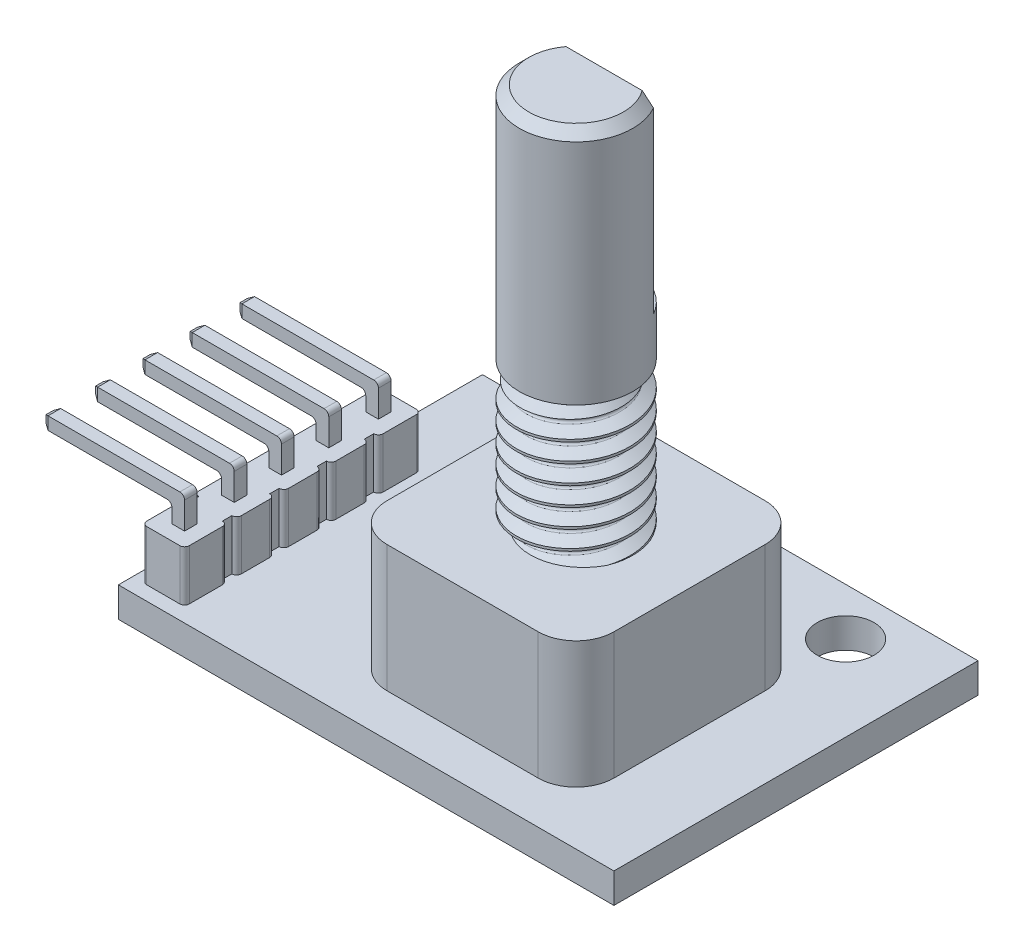
SolidWorks part; units mm, degrees
note: The reader was unsure of these and kept them because the rebuilt part matched: shared geometry of "Esboço2<2>", "Esboço6<3>", "Esboço6<4>".
ref_plane "Plano frontal" through (0, 0, 0) normal (0, 0, 1) x (1, 0, 0)
ref_plane "Plano superior" through (0, 0, 0) normal (0, 1, 0) x (1, 0, 0)
ref_plane "Plano direito" through (0, 0, 0) normal (1, 0, 0) x (0, 0, -1)
sketch "Esboço2" plane through (0, 0, 0) normal (0, 1, 0) x (1, 0, 0)
  line L5 (-6, 6) -> (6, 6)
  line L6 (-6, 6) -> (-6, -6)
  line L7 (-6, -6) -> (6, -6)
  line L8 (6, 6) -> (6, -6)
  line L9 (-6, 6) -> (6, -6) construction
  line L10 (-6, -6) -> (6, 6) construction
  line L11 (-15.95, 11) -> (10.25, 11)
  line L12 (-15.95, 11) -> (-15.95, -8.25)
  line L13 (-15.95, -8.25) -> (10.25, -8.25)
  line L14 (10.25, 11) -> (10.25, -8.25)
  line L15 (-15.95, 11) -> (10.25, -8.25) construction
  line L16 (-15.95, -8.25) -> (10.25, 11) construction
  circle A0 centre (-11.15, 8.5) radius 1.5
  circle A1 centre (5.75, 8.5) radius 1.5
  point P0 (0, 0)
  dimension "D7" = 3
  dimension "D8" = 2.5
  dimension "D9" = 4.5
  dimension "D10" = 16.9
  dimension "D1" = 26.2
  dimension "D2" = 19.25
  dimension "D3" = 12
  dimension "D4" = 12
  dimension "D5" = 5
  dimension "D6" = 4.25
extrude "Ressalto-extrusão1" add sketch "Esboço2" along normal blind 1.58
extrude "Ressalto-extrusão2" add sketch "Esboço2<2>" along normal offset from surface (8.28 mm away) 6.7 contours L8 L5 L6 L7 up to face at (-11.15, 1.58, -7) offset beyond the face yes
sketch "Esboço2<2>" plane through (0, 0, 0) normal (0, 1, 0) x (1, 0, 0) same geometry as "Esboço2"
sketch "Esboço3" plane through (0, 1.58, 0) normal (0, 1, 0) x (1, 0, 0)
  line L0 (-15.45, 2.5) -> (-13.2, 2.5) construction
  line L1 (-15.45, 5) -> (-13.2, 5)
  line L2 (-15.45, 5) -> (-15.45, 2.75)
  line L3 (-15.45, -7.5) -> (-13.2, -7.5)
  line L4 (-13.2, 5) -> (-13.2, 2.75)
  line L5 (-15.45, 0) -> (-13.2, 0) construction
  line L6 (10.25, 11) -> (-15.95, 11) construction
  line L7 (-15.45, -2.5) -> (-13.2, -2.5) construction
  line L9 (-15.45, -5) -> (-13.2, -5) construction
  line L10 (-15.45, 2.25) -> (-15.2, 2.25)
  line L11 (-15.45, -0.25) -> (-15.2, -0.25)
  line L12 (-15.45, -2.75) -> (-15.2, -2.75)
  line L13 (-15.45, -5.25) -> (-15.2, -5.25)
  line L14 (-15.45, 2.75) -> (-15.2, 2.75)
  line L15 (-15.45, 0.25) -> (-15.2, 0.25)
  line L16 (-15.45, -2.25) -> (-15.2, -2.25)
  line L17 (-15.45, -4.75) -> (-15.2, -4.75)
  line L18 (-15.2, 2.75) -> (-15.2, 2.25)
  line L19 (-13.45, 2.75) -> (-13.45, 2.25)
  line L20 (-15.45, 2.25) -> (-15.45, 0.25)
  line L21 (-13.2, 2.25) -> (-13.2, 0.25)
  line L22 (-13.45, 2.25) -> (-13.2, 2.25)
  line L23 (-13.45, 2.75) -> (-13.2, 2.75)
  line L24 (-15.45, 2.25) -> (-13.2, 2.25) construction
  line L25 (-15.2, 0.25) -> (-15.2, -0.25)
  line L26 (-15.45, 2.75) -> (-13.2, 2.75) construction
  line L27 (-13.45, 0.25) -> (-13.45, -0.25)
  line L28 (-13.45, 0.25) -> (-13.2, 0.25)
  line L29 (-13.2, -0.25) -> (-13.2, -2.25)
  line L30 (-15.45, 0.25) -> (-13.2, 0.25) construction
  line L31 (-13.45, -0.25) -> (-13.2, -0.25)
  line L32 (-13.45, -2.25) -> (-13.45, -2.75)
  line L33 (-15.45, -0.25) -> (-13.2, -0.25) construction
  line L34 (-13.2, -2.75) -> (-13.2, -4.75)
  line L35 (-13.45, -2.25) -> (-13.2, -2.25)
  line L36 (-13.45, -2.75) -> (-13.2, -2.75)
  line L37 (-15.45, -2.25) -> (-13.2, -2.25) construction
  line L38 (-13.45, -4.75) -> (-13.45, -5.25)
  line L39 (-15.45, -2.75) -> (-13.2, -2.75) construction
  line L40 (-13.45, -4.75) -> (-13.2, -4.75)
  line L41 (-13.2, -5.25) -> (-13.2, -7.5)
  line L42 (-15.45, -4.75) -> (-13.2, -4.75) construction
  line L43 (-13.45, -5.25) -> (-13.2, -5.25)
  line L44 (-15.45, -5.25) -> (-15.45, -7.5)
  line L45 (-15.45, -5.25) -> (-13.2, -5.25) construction
  line L46 (-15.2, -4.75) -> (-15.2, -5.25)
  line L47 (-15.45, -0.25) -> (-15.45, -2.25)
  line L48 (-15.2, -2.25) -> (-15.2, -2.75)
  line L49 (-15.45, -2.75) -> (-15.45, -4.75)
  line L50 (-15.95, 11) -> (-15.95, -8.25) construction
  dimension "D1" = 12.5
  dimension "D2" = 2.25
  dimension "D3" = 2.25
  dimension "D4" = 2.5
  dimension "D5" = 2.5
  dimension "D6" = 2.5
  dimension "D7" = 6
  dimension "D8" = 0.5
  dimension "D9" = 2.25
  dimension "D12" = 0.25
  dimension "D13" = 0.25
  dimension "D10" = 0.25
  dimension "D11" = 0.25
extrude "Ressalto-extrusão3" add sketch "Esboço3" along normal offset from surface (2.67 mm away) 4.25 up to face at (-2.85, 0, -1.375)
fillet "Filete1" radius 0.25 20 edges at (-13.2, 2.915, -5) (-13.2, 2.915, -2.75) (-13.2, 2.915, -2.25) (-13.2, 2.915, -0.25) (-13.2, 2.915, 0.25) (-13.2, 2.915, 2.25) (-13.2, 2.915, 2.75) (-13.2, 2.915, 5.25) (-13.2, 2.915, 4.75) (-15.45, 2.915, -5) (-15.45, 2.915, -2.75) (-15.45, 2.915, -2.25) (-15.45, 2.915, -0.25) (-15.45, 2.915, 0.25) (-15.45, 2.915, 2.25) (-15.45, 2.915, 2.75) (-15.45, 2.915, 4.75) (-15.45, 2.915, 5.25) (-13.2, 2.915, 7.5) (-15.45, 2.915, 7.5)
sketch "Esboço4" plane through (0, 4.25, 0) normal (0, 1, 0) x (1, 0, 0)
  line L0 (-14.325, 5) -> (-14.325, -7.5) construction
  line L1 (-13.45, 5) -> (-15.2, 5) construction
  line L2 (-15.2, -7.5) -> (-13.45, -7.5) construction
  line L4 (-15.45, -5.5) -> (-15.45, -7.25) construction
  line L5 (-15.45, -6.375) -> (-13.2, -6.375) construction
  line L6 (-13.2, -7.25) -> (-13.2, -5.5) construction
  line L7 (-14.66, 4.21) -> (-13.99, 4.21)
  line L8 (-15.45, -3) -> (-15.45, -4.5) construction
  line L9 (-15.45, -3.75) -> (-13.2, -3.75) construction
  line L10 (-13.2, -4.5) -> (-13.2, -3) construction
  line L11 (-14.66, 4.21) -> (-14.66, 3.54)
  line L12 (-15.45, -0.5) -> (-15.45, -2) construction
  line L13 (-15.45, -1.25) -> (-13.2, -1.25) construction
  line L14 (-13.2, -2) -> (-13.2, -0.5) construction
  line L15 (-14.66, 3.54) -> (-13.99, 3.54)
  line L16 (-15.45, 2) -> (-15.45, 0.5) construction
  line L17 (-15.45, 1.25) -> (-13.2, 1.25) construction
  line L18 (-13.2, 0.5) -> (-13.2, 2) construction
  line L19 (-13.99, 4.21) -> (-13.99, 3.54)
  line L20 (-15.45, 4.75) -> (-15.45, 3) construction
  line L21 (-15.45, 3.875) -> (-13.2, 3.875) construction
  line L22 (-13.2, 3) -> (-13.2, 4.75) construction
  line L23 (-14.66, 4.21) -> (-13.99, 3.54) construction
  line L24 (-14.66, 3.54) -> (-13.99, 4.21) construction
  line L25 (-14.66, 1.585) -> (-13.99, 1.585)
  line L26 (-14.66, 1.585) -> (-14.66, 0.915)
  line L27 (-14.66, 0.915) -> (-13.99, 0.915)
  line L28 (-13.99, 1.585) -> (-13.99, 0.915)
  line L29 (-14.66, 1.585) -> (-13.99, 0.915) construction
  line L30 (-14.66, 0.915) -> (-13.99, 1.585) construction
  line L31 (-14.66, -0.915) -> (-13.99, -0.915)
  line L32 (-14.66, -0.915) -> (-14.66, -1.585)
  line L33 (-14.66, -1.585) -> (-13.99, -1.585)
  line L34 (-13.99, -0.915) -> (-13.99, -1.585)
  line L35 (-14.66, -0.915) -> (-13.99, -1.585) construction
  line L36 (-14.66, -1.585) -> (-13.99, -0.915) construction
  line L37 (-14.66, -3.415) -> (-13.99, -3.415)
  line L38 (-14.66, -3.415) -> (-14.66, -4.085)
  line L39 (-14.66, -4.085) -> (-13.99, -4.085)
  line L40 (-13.99, -3.415) -> (-13.99, -4.085)
  line L41 (-14.66, -3.415) -> (-13.99, -4.085) construction
  line L42 (-14.66, -4.085) -> (-13.99, -3.415) construction
  line L43 (-14.66, -6.04) -> (-13.99, -6.04)
  line L44 (-14.66, -6.04) -> (-14.66, -6.71)
  line L45 (-14.66, -6.71) -> (-13.99, -6.71)
  line L46 (-13.99, -6.04) -> (-13.99, -6.71)
  line L47 (-14.66, -6.04) -> (-13.99, -6.71) construction
  line L48 (-14.66, -6.71) -> (-13.99, -6.04) construction
  point P6 (-14.325, 3.875)
  point P41 (-14.325, 1.25)
  point P46 (-14.325, -1.25)
  point P51 (-14.325, -3.75)
  point P56 (-14.325, -6.375)
  dimension "D1" = 0.67
extrude "Ressalto-extrusão4" add sketch "Esboço4" along normal blind 1.67
sketch "Esboço5" plane through (-14.66, 0, 0) normal (-1, 0, 0) x (0, 0, 1)
  line L1 (6.71, 4.25) -> (6.71, 5.92) construction
  line L2 (6.71, 5.92) -> (6.04, 5.92) construction
  line L3 (6.04, 5.92) -> (6.04, 4.25) construction
  line L5 (4.085, 4.25) -> (4.085, 5.92) construction
  line L6 (4.085, 5.92) -> (3.415, 5.92) construction
  line L7 (3.415, 5.92) -> (3.415, 4.25) construction
  line L9 (1.585, 4.25) -> (1.585, 5.92) construction
  line L10 (1.585, 5.92) -> (0.915, 5.92) construction
  line L11 (0.915, 5.92) -> (0.915, 4.25) construction
  line L13 (-0.915, 4.25) -> (-0.915, 5.92) construction
  line L14 (-0.915, 5.92) -> (-1.585, 5.92) construction
  line L15 (-1.585, 5.92) -> (-1.585, 4.25) construction
  line L17 (-3.54, 4.25) -> (-3.54, 5.92) construction
  line L18 (-3.54, 5.92) -> (-4.21, 5.92) construction
  line L19 (-4.21, 5.92) -> (-4.21, 4.25) construction
  line L21 (6.71, 5.25) -> (6.71, 5.92)
  line L22 (6.71, 5.92) -> (6.04, 5.92)
  line L23 (6.04, 5.92) -> (6.04, 5.25)
  line L25 (4.085, 5.25) -> (4.085, 5.92)
  line L26 (4.085, 5.92) -> (3.415, 5.92)
  line L27 (3.415, 5.92) -> (3.415, 5.25)
  line L29 (1.585, 5.25) -> (1.585, 5.92)
  line L30 (1.585, 5.92) -> (0.915, 5.92)
  line L31 (0.915, 5.92) -> (0.915, 5.25)
  line L33 (-0.915, 5.25) -> (-0.915, 5.92)
  line L34 (-0.915, 5.92) -> (-1.585, 5.92)
  line L35 (-1.585, 5.92) -> (-1.585, 5.25)
  line L37 (-3.54, 5.25) -> (-3.54, 5.92)
  line L38 (-3.54, 5.92) -> (-4.21, 5.92)
  line L39 (-4.21, 5.92) -> (-4.21, 5.25)
  line L40 (-4.21, 5.25) -> (-3.54, 5.25)
  line L41 (-1.585, 5.25) -> (-0.915, 5.25)
  line L42 (0.915, 5.25) -> (1.585, 5.25)
  line L43 (6.04, 5.25) -> (6.71, 5.25)
  line L44 (3.415, 5.25) -> (4.085, 5.25)
  dimension "D1" = 0.67
extrude "Ressalto-extrusão5" add sketch "Esboço5" along normal blind 6.8
fillet "Filete2" radius 0.25 10 edges at (-14.66, 5.25, 6.375) (-13.99, 5.92, 6.375) (-13.99, 5.92, 3.75) (-14.66, 5.25, 3.75) (-14.66, 5.25, 1.25) (-13.99, 5.92, 1.25) (-14.66, 5.25, -1.25) (-13.99, 5.92, -1.25) (-13.99, 5.92, -3.875) (-14.66, 5.25, -3.875)
chamfer "Chanfro1" distance 0.25 angle 30 20 edges at (-21.46, 5.585, 6.71) (-21.46, 5.25, 6.375) (-21.46, 5.585, 6.04) (-21.46, 5.92, 6.375) (-21.46, 5.25, 3.75) (-21.46, 5.585, 4.085) (-21.46, 5.92, 3.75) (-21.46, 5.585, 3.415) (-21.46, 5.585, 1.585) (-21.46, 5.25, 1.25) (-21.46, 5.585, 0.915) (-21.46, 5.92, 1.25) (-21.46, 5.25, -1.25) (-21.46, 5.585, -0.915) (-21.46, 5.92, -1.25) (-21.46, 5.585, -1.585) (-21.46, 5.25, -3.875) (-21.46, 5.585, -3.54) (-21.46, 5.92, -3.875) (-21.46, 5.585, -4.21) first distance on face at (-16.1583, 5.2017, 6.71) first distance on face at (-18.185, 5.25, 6.375) first distance on face at (-16.1583, 5.2017, 6.04) first distance on face at (-17.85, 5.92, 6.375) first distance on face at (-18.185, 5.25, 3.75) first distance on face at (-16.1583, 5.2017, 4.085) first distance on face at (-17.85, 5.92, 3.75) first distance on face at (-16.1583, 5.2017, 3.415) first distance on face at (-16.1583, 5.2017, 1.585) first distance on face at (-18.185, 5.25, 1.25) first distance on face at (-16.1583, 5.2017, 0.915) first distance on face at (-17.85, 5.92, 1.25) first distance on face at (-18.185, 5.25, -1.25) first distance on face at (-16.1583, 5.2017, -0.915) first distance on face at (-17.85, 5.92, -1.25) first distance on face at (-16.1583, 5.2017, -1.585) first distance on face at (-18.185, 5.25, -3.875) first distance on face at (-16.1583, 5.2017, -3.54) first distance on face at (-17.85, 5.92, -3.875) first distance on face at (-16.1583, 5.2017, -4.21)
sketch "Esboço6" plane through (0, 8.28, 0) normal (0, 1, 0) x (1, 0, 0)
  circle A0 centre (0, 0) radius 3
  circle A1 centre (0, 0) radius 1.5
  dimension "D1" = 6
  dimension "D2" = 3
extrude "Ressalto-extrusão6" add sketch "Esboço6" along normal blind 7 contours A1 | A0 A1
extrude "Ressalto-extrusão7" add sketch "Esboço6<3>" along normal blind 0.5 from surface at 7 contours A1 starting at face at (0, 15.28, 3)
sketch "Esboço6<3>" plane through (0, 8.28, 0) normal (0, 1, 0) x (1, 0, 0) same geometry as "Esboço6"
extrude "Ressalto-extrusão8" add sketch "Esboço6<4>" along normal blind 2.6 from surface at 7.5 contours A0 A1 | A1 starting at face at (0, 15.78, 1.5)
sketch "Esboço6<4>" plane through (0, 8.28, 0) normal (0, 1, 0) x (1, 0, 0) same geometry as "Esboço6"
sketch "Esboço7" plane through (0, 18.38, 0) normal (0, 1, 0) x (1, 0, 0)
  line L0 (-2.6095, 1.48) -> (2.6095, 1.48)
  circle A0 centre (0, 0) radius 3 construction
  circle A1 centre (0, 0) radius 3 construction
  arc A2 (-2.6095, 1.48) -> (2.6095, 1.48) centre (0, 0) ccw
  point P6 (0, -3)
  dimension "D1" = 4.48
extrude "Ressalto-extrusão9" add sketch "Esboço7" along normal blind 9.95
chamfer "Chanfro2" distance 0.5 angle 45 1 edges at (0, 28.33, 3)
fillet "Filete3" radius 2 4 edges at (6, 4.93, -6) (6, 4.93, 6) (-6, 4.93, 6) (-6, 4.93, -6)
sketch "Esboço8" plane through (0, 15.28, 0) normal (0, 1, 0) x (1, 0, 0)
  circle A1 centre (0, 0) radius 3
  circle A2 centre (0, 0) radius 3
  dimension "D1" = 0
curve "Hélice/Espiral1" pitch 1 height 7 turns 7
chamfer "Chanfro3" distance 0.7 1 edges at (0, 15.28, 3)
sketch "Esboço9" plane through (0, 0, 0) normal (0, 0, 1) x (1, 0, 0)
  line L0 (-3, 15.7175) -> (-3, 14.8425)
  line L3 (-3, 15.28) -> (-2.3866, 15.28) construction
  line L4 (-2.3866, 15.28) -> (0, 15.28) construction
  line L5 (-3, 15.7175) -> (-3, 15.78) construction
  line L6 (-3, 27.83) -> (-3, 15.78) construction
  line L7 (-3, 14.8425) -> (-3, 14.78) construction
  line L8 (-3, 14.58) -> (-3, 8.28) construction
  line L9 (-2.3866, 15.28) -> (-2.2423, 15.28) construction
  line L10 (-3, 15.7175) -> (-2.2423, 15.28) construction
  line L11 (3, 15.28) -> (-3, 15.28) construction
  line L12 (-3, 14.8425) -> (-2.2423, 15.28) construction
  line L13 (-3, 15.7175) -> (-2.4588, 15.405)
  line L14 (-3, 14.8425) -> (-2.4588, 15.155)
  arc A0 (-2.4588, 15.155) -> (-2.4588, 15.405) centre (-2.5309, 15.28) ccw
  dimension "D4" = 0.2887
  dimension "D1" = 2.3866
  dimension "D2" = 60
  dimension "D3" = 1
sweep "Varredura de corte1" cut profiles "Esboço9" path "Hélice/Espiral1" align with end faces yes
